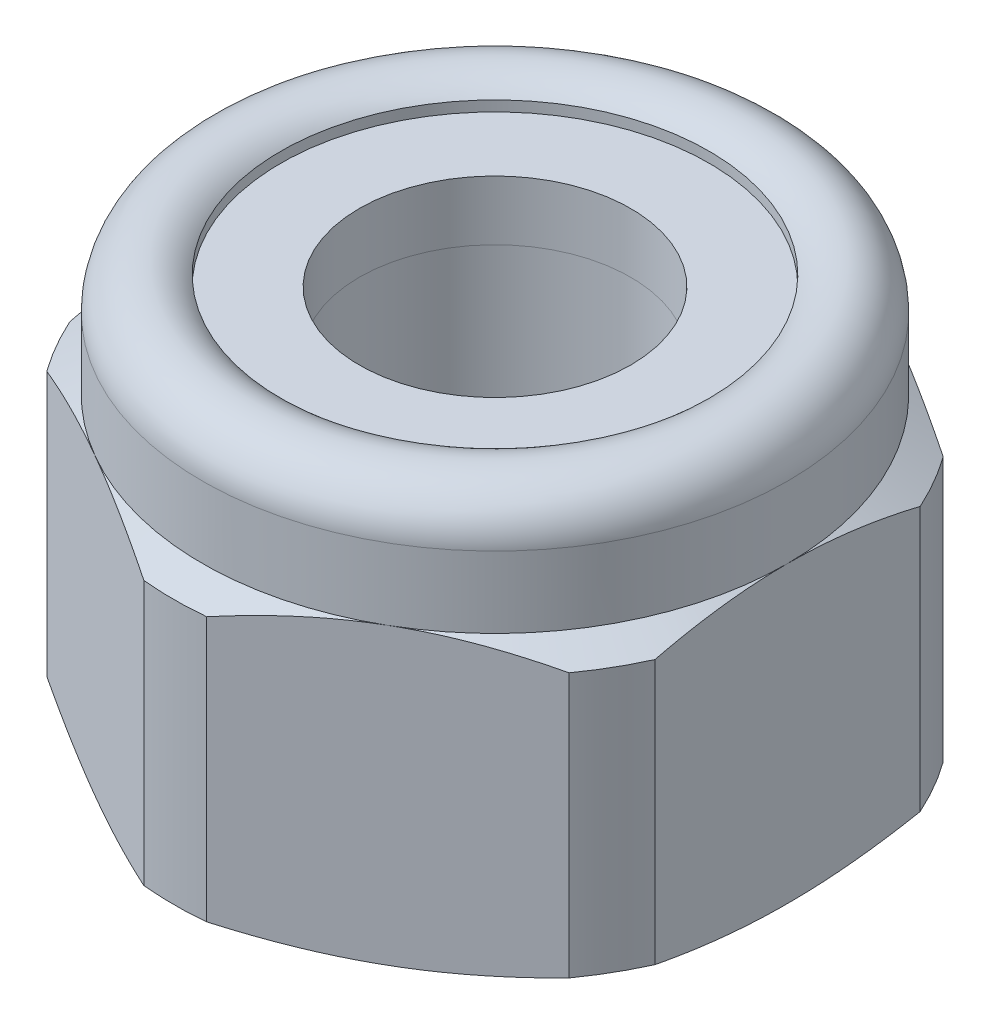
SolidWorks part; units mm, degrees
material "Alloy Steel (SS)"
ref_plane "Front Plane" through (0, 0, 0) normal (0, 0, 1) x (1, 0, 0)
ref_plane "Top Plane" through (0, 0, 0) normal (0, 1, 0) x (1, 0, 0)
ref_plane "Right Plane" through (0, 0, 0) normal (1, 0, 0) x (0, 0, -1)
sketch "Sketch1" plane through (0, 0, 0) normal (0, 0, 1) x (1, 0, 0)
  line L0 (0, -3.9751) -> (0, 3.9751) construction
  line L1 (5.5753, 0) -> (-5.5753, 0) construction
  line L2 (3.175, -3.9751) -> (-3.175, -3.9751) construction
  line L3 (3.175, -3.9751) -> (3.175, -3.068) construction
  line L4 (-6.1214, -3.9751) -> (6.1214, -3.9751) construction
  line L5 (-6.1214, -3.9751) -> (-6.1214, 1.7399) construction
  point P4 (0, 0)
  point P8 (0, 0)
  point P11 (0, -3.9751)
  dimension "Height" = 7.9502
  dimension "Width" = 11.1506
  dimension "Thread Size" = 6.35
  dimension "Thread Pitch" = 0.9071
  dimension "C (ref)" = 12.2428
  dimension "D (ref)" = 5.715
sketch "Sketch2" plane through (0, 0, 0) normal (0, 1, 0) x (1, 0, 0)
  line L0 (-3.175, 0.3969) -> (-3.175, -0.3969) construction
  line L1 (0, 6.4378) -> (-5.5753, 3.2189)
  line L2 (-5.5753, 3.2189) -> (-5.5753, -3.2189)
  line L3 (-5.5753, -3.2189) -> (0, -6.4378)
  line L4 (0, -6.4378) -> (5.5753, -3.2189)
  line L5 (5.5753, -3.2189) -> (5.5753, 3.2189)
  line L6 (5.5753, 3.2189) -> (0, 6.4378)
  line L7 (-3.175, -0.3969) -> (-2.5858, -0.0567) construction
  line L8 (-2.5858, -0.0567) -> (-2.5858, 0.0567) construction
  line L9 (-2.5858, 0.0567) -> (-3.175, 0.3969) construction
  line L10 (-2.5858, 0) -> (-3.175, 0) construction
  line L11 (-2.8804, 0.2268) -> (-2.8804, -0.2268) construction
  line L12 (3.175, 0) -> (-3.175, 0) construction
  line L13 (5.5753, 0) -> (-5.5753, 0) construction
  circle A0 centre (0, 0) radius 5.5753 construction
  circle A1 centre (0, 0) radius 2.5858
  point P19 (0, -2.5858)
  dimension "D1" = 0.1134
  dimension "D2" = 0.4536
  dimension "D3" = 60
extrude "Boss-Extrude1" add sketch "Sketch2" along normal up to vertex (3.9751 mm away) and the other way up to vertex (3.9751 mm away) up to point (0, 3.9751, 0) other way up to point (0, -3.9751, 0)
sketch "Sketch3" plane through (0, 0, 0) normal (1, 0, 0) x (0, 0, -1)
  line L0 (6.4378, 1.7399) -> (6.4378, 4.9751)
  line L1 (4.0805, 2.3851) -> (5.5753, 2.3851) construction
  line L2 (5.3523, -3.9751) -> (6.4378, -3.4689)
  line L3 (3.2189, -3.9751) -> (6.4378, -3.9751) construction
  line L4 (6.4378, 3.9751) -> (6.4378, -3.9751) construction
  line L5 (6.4378, -3.4689) -> (6.4378, -3.9751)
  line L6 (6.4378, -3.9751) -> (5.3523, -3.9751)
  line L7 (5.5753, 1.7399) -> (6.4378, 1.2337)
  line L8 (6.4378, 1.2337) -> (6.4378, 1.7399)
  line L9 (5.5753, 2.3851) -> (5.5753, 1.7399) construction
  line L10 (3.2189, -3.9751) -> (6.4378, -3.9751) construction
  line L11 (5.5753, 1.7399) -> (5.5753, 3.0995)
  line L12 (3.2189, 3.9751) -> (6.4378, 3.9751) construction
  line L13 (2.5858, 2.3851) -> (4.0805, 2.3851)
  line L14 (4.0805, 2.3851) -> (4.0805, 3.7186)
  line L16 (4.0805, 3.7186) -> (4.6997, 3.0995) construction
  line L17 (4.6997, 3.0995) -> (4.6997, 3.9751) construction
  line L18 (2.5858, 2.3851) -> (2.5858, 4.9751)
  line L19 (2.5858, 4.9751) -> (6.4378, 4.9751)
  line L21 (2.5858, -3.9751) -> (2.5858, -3.3401)
  line L22 (-3.2189, -3.9751) -> (3.2189, -3.9751) construction
  line L24 (3.2208, -3.9751) -> (2.5858, -3.9751)
  line L25 (2.5858, -3.3401) -> (3.2208, -3.9751)
  line L26 (6.4378, -3.9751) -> (3.2189, -3.9751) construction
  arc A0 (5.5753, 3.0995) -> (4.0805, 3.7186) centre (4.6997, 3.0995) ccw
  point P0 (5.5753, 1.7399)
  point P1 (5.5753, 0)
  point P14 (2.5858, 0)
  point P36 (5.5753, -3.9751)
  dimension "D2" = 25
  dimension "D3" = 45
  dimension "D4" = 1
  dimension "D5" = 0.635
  dimension "D6" = 6.3602
  dimension "D7" = 0.223
  dimension "D1" = 5.715
revolve "Cut-Revolve2" cut sketch "Sketch3" angle 360 about L0
sketch "Sketch4" plane through (0, 0, 0) normal (1, 0, 0) x (0, 0, -1)
  line L0 (-4.0805, 3.7186) -> (-4.0805, 2.3851) construction
  line L1 (-2.5858, 2.3851) -> (-4.0805, 2.3851)
  line L2 (-2.5858, 2.3851) -> (-2.5858, 3.5199)
  line L3 (-2.5858, 3.5199) -> (-4.0805, 3.5199)
  line L4 (-4.0805, 2.3851) -> (-4.0805, 3.5199)
  line L5 (4.0805, 3.7186) -> (-4.0805, 3.7186) construction
  line L6 (2.5858, 2.3851) -> (-2.5858, 2.3851) construction
  dimension "D1" = 0.1988
revolve "Revolve1" add sketch "Sketch4" angle 360 about L0
sketch "Sketch5" plane through (0, 0, 0) normal (0, 1, 0) x (1, 0, 0)
  circle A0 centre (0, 0) radius 2.5858 construction
  point P0 (0, -2.5858)
sketch "Sketch11" plane through (0, -3.9751, 0) normal (0, -1, 0) x (1, 0, 0)
  circle A0 centre (0, 0) radius 6.1214
extrude "Cut-Extrude1" cut sketch "Sketch11" against normal through all flip side to cut
sketch "Sketch6" [suppressed] plane through (0, 0, 0) normal (0, 0, 1) x (1, 0, 0)
  line L0 (3.175, 2.3851) -> (3.175, -3.9751)
  line L2 (0, -3.9751) -> (5.5753, -3.9751) construction
  line L3 (3.175, -3.9751) -> (0, -3.9751)
  line L4 (0, -3.9751) -> (0, 2.3851)
  line L5 (0, -3.9751) -> (0, 3.9751) construction
  line L6 (0, 2.3851) -> (3.175, 2.3851)
  point P1 (0, 2.3851)
revolve "Revolve2" [suppressed] add sketch "Sketch6" angle 360 about L4
sketch "Sketch7" [suppressed] plane through (0, -3.9751, 0) normal (0, -1, 0) x (1, 0, 0)
  circle A2 centre (0, 0) radius 3.175
  circle A3 centre (0, 0) radius 3.175
  dimension "D1" = 0
curve "Helix/Spiral1" [suppressed] pitch 0.9071 height 7.9502 turns 8.764
sketch "Sketch8" [suppressed] plane through (0, 0, 0) normal (0, 0, 1) x (1, 0, 0)
  line L0 (3.2732, -3.9184) -> (2.4876, -4.372) construction
  line L1 (2.4876, -4.372) -> (3.2732, -4.8255) construction
  line L2 (3.2732, -4.8255) -> (3.2732, -3.9184) construction
  line L3 (2.5858, -4.3153) -> (2.5858, -4.4287)
  line L4 (3.175, -3.9751) -> (3.175, -4.7689) construction
  line L5 (3.175, -4.372) -> (3.2732, -4.372) construction
  line L6 (2.4876, -4.372) -> (2.5858, -4.372) construction
  line L7 (3.2241, -4.372) -> (3.2241, -4.7972) construction
  line L8 (2.5858, -4.3153) -> (3.2732, -3.9184)
  line L9 (3.2732, -3.9184) -> (3.2241, -4.7972)
  line L10 (2.5858, -4.4287) -> (3.2241, -4.7972)
  dimension "D1" = 0.9071
  dimension "D2" = 0.1134
sweep "Cut-Sweep1" [suppressed] cut profiles "Sketch8" path "Helix/Spiral1"
sketch "Sketch9" [suppressed] plane through (0, 0, 0) normal (0, 0, 1) x (1, 0, 0)
  line L0 (0, -0.8001) -> (0, -3.9751)
  line L1 (0, -0.8001) -> (0, -0.1651)
  line L2 (0, -3.9751) -> (3.175, -3.9751)
  line L3 (3.175, -3.9751) -> (3.81, -3.9751)
  line L4 (3.81, -3.9751) -> (0, -0.1651)
  dimension "D1" = 0.635
revolve "Revolve3" [suppressed] add sketch "Sketch9" angle 360 about L0
sketch "Sketch10" [suppressed] plane through (0, -3.9751, 0) normal (0, -1, 0) x (1, 0, 0)
  circle A0 centre (0, 0) radius 3.2208 construction
  circle A1 centre (0, 0) radius 3.2208
extrude "Boss-Extrude2" [suppressed] add sketch "Sketch10" against normal up to surface (6.3602 mm away)
combine bodies "Combine1" [suppressed] operation type subtract main body 110 bodies to subtract 109
equation "\"D5@Sketch3\"=\"Thread Size@Sketch1\"*.1"
equation "\"D4@Helix/Spiral1\" = \"Thread Pitch@Sketch1\""
equation "\"D3@Helix/Spiral1\" = \"Height@Sketch1\""
equation "\"D1@Sketch8\" = \"Thread Pitch@Sketch1\""
equation "\"D2@Sketch8\" = \"Thread Pitch@Sketch1\" / 8"
equation "\"D1@Sketch9\"=\"Thread Size@Sketch1\" * .1"
equation "\"D1@Sketch2\" = \"Thread Pitch@Sketch1\" / 8"
equation "\"D2@Sketch2\" = \"Thread Pitch@Sketch1\" / 2"
equation "\"D1@Sketch4\"=\"Height@Sketch1\" * .025"
equation "\"D6@Sketch3\"=\"Height@Sketch1\" *.8"
equation "\"D7@Sketch3\"=\"Width@Sketch1\"*.02"
equation "\"D1@Sketch3\" = \"D (ref)@Sketch1\""
